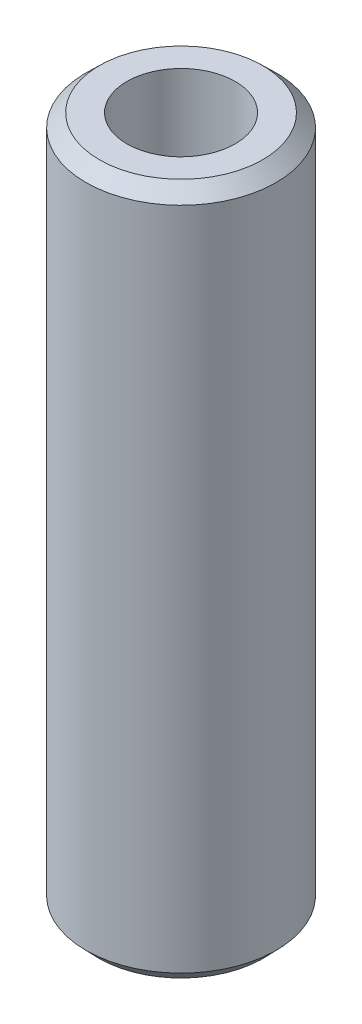
SolidWorks part; units mm, degrees
ref_plane "Front Plane" through (0, 0, 0) normal (0, 0, 1) x (1, 0, 0)
ref_plane "Top Plane" through (0, 0, 0) normal (0, 1, 0) x (1, 0, 0)
ref_plane "Right Plane" through (0, 0, 0) normal (1, 0, 0) x (0, 0, -1)
sketch "Sketch1" plane through (0, 0, 0) normal (0, 1, 0) x (1, 0, 0)
  circle A0 centre (0, 0) radius 27.5
  dimension "SHAFT_OD" = 55
extrude "Boss-Extrude1" add sketch "Sketch1" along normal blind 199.9632
sketch "Sketch2" plane through (0, 0, 0) normal (0, 1, 0) x (1, 0, 0)
  circle A0 centre (0, 0) radius 15.6557
  dimension "BORE_D" = 31.3115
extrude "Cut-Extrude1" cut sketch "Sketch2" along normal through all
chamfer "Chamfer1" distance 3.7612 angle 45.969 2 edges at (0, 199.9632, 27.5) (0, 0, 27.5) first distance on face at (0, 199.9632, 27.5) first distance on face at (0, 0, 15.6557)
